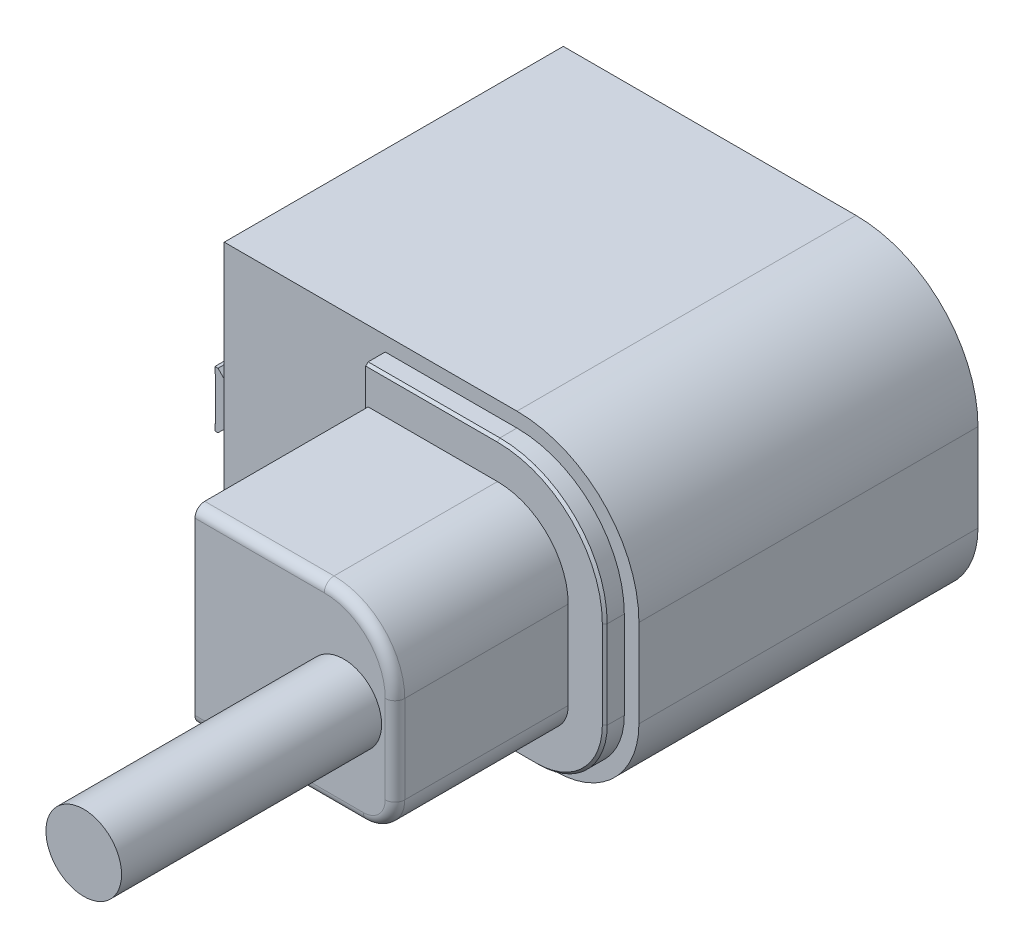
SolidWorks part; units mm, degrees
ref_plane "Front Plane" through (0, 0, 0) normal (0, 0, 1) x (1, 0, 0)
ref_plane "Top Plane" through (0, 0, 0) normal (0, 1, 0) x (1, 0, 0)
ref_plane "Right Plane" through (0, 0, 0) normal (1, 0, 0) x (0, 0, -1)
sketch "Sketch1" plane through (0, 0, 0) normal (0, 0, 1) x (1, 0, 0)
  line L0 (0, 38.0675) -> (0, -37.7433) construction
  line L1 (-42.5, 30) -> (42.5, 30)
  line L2 (42.5, 30) -> (42.5, -30)
  line L3 (42.5, -30) -> (-42.5, -30)
  line L4 (-42.5, -30) -> (-42.5, 30)
  dimension "D1" = 85
  dimension "D2" = 60
  dimension "D3" = 30
  dimension "D4" = 42.5
extrude "Boss-Extrude1" add sketch "Sketch1" along normal blind 69.5
sketch "Sketch2" plane through (0, 0, 69.5) normal (0, 0, 1) x (1, 0, 0)
  line L0 (-42.5, 0) -> (-55.2274, 0) construction
  line L1 (-42.5, 30) -> (-42.5, -30) construction
  line L6 (-42.5, 3.495) -> (-42.79, 3.495)
  line L7 (-42.79, 3.495) -> (-45.03, 5.73)
  line L8 (-45.03, 5.73) -> (-45.66, 5.73)
  line L9 (-45.66, 5.73) -> (-45.66, 4.45)
  line L10 (-45.66, 4.45) -> (-45.5331, 4.45)
  line L11 (-45.5331, 4.45) -> (-45.5331, -4.45)
  line L12 (-42.5, 3.495) -> (-42.5, -3.495)
  line L13 (-45.66, -4.45) -> (-45.5331, -4.45)
  line L14 (-45.66, -5.73) -> (-45.66, -4.45)
  line L15 (-45.03, -5.73) -> (-45.66, -5.73)
  line L16 (-42.79, -3.495) -> (-45.03, -5.73)
  line L17 (-42.5, -3.495) -> (-42.79, -3.495)
  point P14 (-45.5331, 0)
  dimension "D1" = 1.28
  dimension "D2" = 0.63
  dimension "D3" = 2.24
  dimension "D4" = 0.29
  dimension "D5" = 3.495
  dimension "D6" = 5.73
extrude "Boss-Extrude2" add sketch "Sketch2" against normal blind 66.05
sketch "Sketch3" plane through (0, -30, 0) normal (0, -1, 0) x (1, 0, 0)
  line L0 (-42.5, 69.5) -> (-42.5, 68.25)
  line L1 (-42.5, 69.5) -> (-42.5, 0) construction
  line L2 (-42.5, 68.25) -> (-45.66, 68.25)
  line L3 (-45.66, 3.45) -> (-45.66, 69.5) construction
  line L4 (-45.66, 68.25) -> (-45.66, 69.5)
  line L5 (-45.66, 69.5) -> (-42.5, 69.5)
  dimension "D1" = 1.25
extrude "Cut-Extrude1" cut sketch "Sketch3" against normal through all
sketch "Sketch4" plane through (-42.5, 0, 0) normal (-1, 0, 0) x (0, 0, 1)
  line L0 (0, 0) -> (69.5, 0) construction
  line L1 (69.5, 30) -> (69.5, -30) construction
  line L2 (3.45, 2.7) -> (14.31, 5.73)
  line L3 (3.45, 4.45) -> (3.45, -4.45) construction
  line L4 (3.45, 5.73) -> (68.25, 5.73) construction
  line L5 (14.31, 5.73) -> (3.45, 5.73)
  line L6 (3.45, 5.73) -> (3.45, 2.7)
  line L7 (3.45, -5.73) -> (3.45, -2.7)
  line L8 (14.31, -5.73) -> (3.45, -5.73)
  line L9 (3.45, -2.7) -> (14.31, -5.73)
  dimension "D1" = 10.86
  dimension "D2" = 3.03
extrude "Cut-Extrude2" cut sketch "Sketch4" along normal through all
sketch "Sketch5" plane through (0, 0, 69.5) normal (0, 0, 1) x (1, 0, 0)
  line L0 (42.5, 30) -> (-42.5, 30) construction
  line L1 (42.5, -30) -> (42.5, 30) construction
  line L2 (-42.5, -30) -> (42.5, -30) construction
  line L4 (42.5, -13) -> (42.5, -30)
  line L5 (42.5, -30) -> (25.5, -30)
  line L7 (17.5, 30) -> (42.5, 30)
  line L8 (42.5, 30) -> (42.5, 5)
  arc A0 (17.5, 30) -> (42.5, 5) centre (17.5, 5) cw
  arc A1 (42.5, -13) -> (25.5, -30) centre (25.5, -13) cw
  line M2 (-42.5, -30) -> (42.5, -30)
  line M3 (42.5, -30) -> (42.5, 30)
  line M4 (42.5, 30) -> (-42.5, 30)
  dimension "D3" = 25
  dimension "D6" = 17
  dimension "D1" = 25
  dimension "D2" = 25
  dimension "D4" = 17
  dimension "D5" = 17
extrude "Cut-Extrude3" cut sketch "Sketch5" against normal through all contours A0 M4 | A1 M3 M2 region at (38.7027, -26.2027, 69.5) region at (36.9158, 24.4158, 69.5)
sketch "Sketch6" plane through (0, 0, 69.5) normal (0, 0, 1) x (1, 0, 0)
  line L0 (17.5, 27) -> (-9.5, 27)
  line L1 (-9.5, 27) -> (-9.5, -27)
  line L2 (-9.5, -27) -> (17.3085, -27)
  line L3 (17.5, 30) -> (-42.5, 30) construction
  line L5 (17.3085, -27) -> (25.5, -27)
  line L6 (39.5, 5) -> (39.5, -13)
  arc A4 (39.5, 5) -> (17.5, 27) centre (17.5, 5) ccw
  arc A7 (25.5, -27) -> (39.5, -13) centre (25.5, -13) ccw
  dimension "D1" = 54
  dimension "D2" = 27
  dimension "D3" = 3
extrude "Boss-Extrude3" add sketch "Sketch6" along normal blind 4
chamfer "Chamfer1" distance 0.5 angle 45 5 edges at (8, -27, 73.5) (35.3995, -22.8995, 73.5) (39.5, -4, 73.5) (33.0563, 20.5563, 73.5) (4, 27, 73.5)
sketch "Sketch7" plane through (0, 0, 73.5) normal (0, 0, 1) x (1, 0, 0)
  line L3 (-9, 19.5) -> (-9, -19.5)
  line L4 (-9.5, 26.5) -> (-9.5, -26.5) construction
  line L6 (-9.5, -19.5) -> (25.5, -19.5)
  line L7 (32, -13) -> (32, 5)
  line L8 (17.5, 19.5) -> (-9.5, 19.5)
  line L9 (-9, -19.5) -> (25.5, -19.5)
  line L10 (32, -13) -> (32, 5)
  line L11 (17.5, 19.5) -> (-9, 19.5)
  arc A4 (25.5, -19.5) -> (32, -13) centre (25.5, -13) ccw
  arc A5 (32, 5) -> (17.5, 19.5) centre (17.5, 5) ccw
  arc A6 (25.5, -19.5) -> (32, -13) centre (25.5, -13) ccw
  arc A7 (32, 5) -> (17.5, 19.5) centre (17.5, 5) ccw
  dimension "D2" = 0.5
  dimension "D1" = 7
extrude "Boss-Extrude4" add sketch "Sketch7" along normal blind 35.5
sketch "Sketch8" plane through (0, 0, 109) normal (0, 0, 1) x (1, 0, 0)
  line L0 (32, -13) -> (32, 5) construction
  line L1 (17.5, 19.5) -> (-9, 19.5) construction
  circle A0 centre (21.5, 0) radius 7.75
  dimension "D1" = 15.5
  dimension "D2" = 10.5
  dimension "D3" = 19.5
extrude "Boss-Extrude5" add sketch "Sketch8" along normal blind 53.3 contours A0
fillet "Fillet1" radius 2 5 edges at (4.25, 19.5, 109) (27.753, 15.253, 109) (32, -4, 109) (30.0962, -17.5962, 109) (8.25, -19.5, 109)
sketch "Sketch9" plane through (-45.5331, 0, 0) normal (-1, 0, 0) x (0, 0, 1)
  line L0 (0, 0) -> (69.5, 0) construction
  line L1 (69.5, 30) -> (69.5, -30) construction
  line L2 (0, 30) -> (0, -30) construction
  circle A0 centre (55, 0) radius 2
  circle A1 centre (35, 0) radius 2
  dimension "D1" = 4
  dimension "D2" = 4
  dimension "D3" = 35
  dimension "D4" = 55
extrude "Cut-Extrude4" cut sketch "Sketch9" against normal blind 10
sketch "Sketch10" plane through (0, 0, 0) normal (0, 0, -1) x (-1, 0, 0)
  line L0 (42.5, 30) -> (42.5, -30) construction
  line L1 (42.5, -30) -> (-25.5, -30) construction
  circle A0 centre (-16.5, -4) radius 21.5
  dimension "D1" = 59
  dimension "D2" = 26
